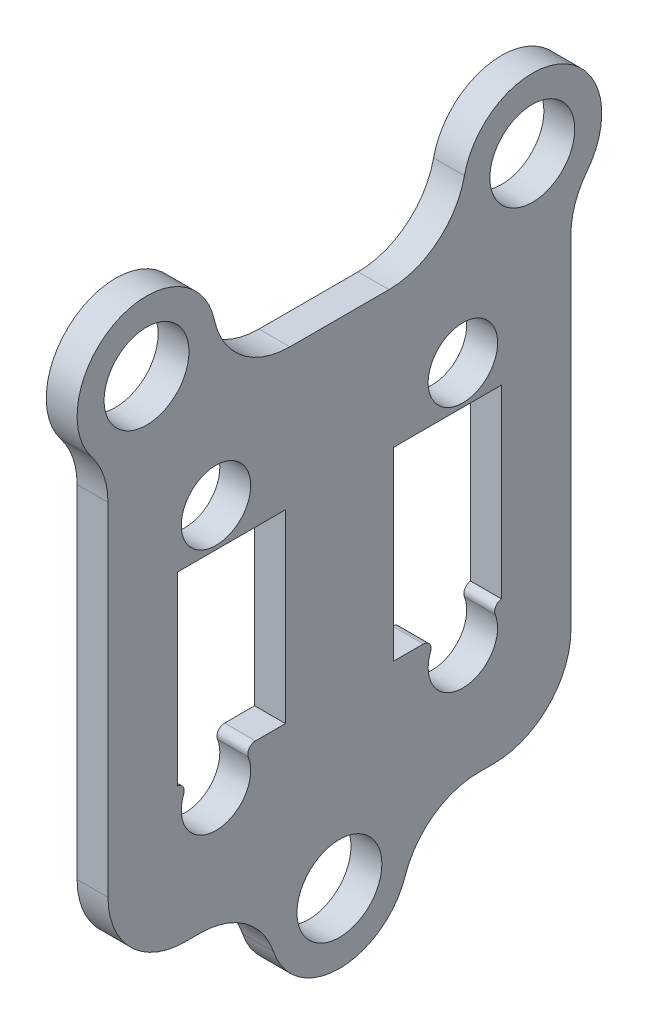
SolidWorks part; units mm, degrees
material "ABS"
ref_plane "Front Plane" through (0, 0, 0) normal (0, 0, 1) x (1, 0, 0)
ref_plane "Top Plane" through (0, 0, 0) normal (0, 1, 0) x (1, 0, 0)
ref_plane "Right Plane" through (0, 0, 0) normal (1, 0, 0) x (0, 0, -1)
sketch "Sketch1" plane through (0, 0, 0) normal (1, 0, 0) x (0, 0, -1)
  line L1 (-15, -15) -> (15, -15)
  line L2 (-15, -15) -> (-15, 15)
  line L3 (-15, 15) -> (15, 15)
  line L4 (15, -15) -> (15, 15)
  line L5 (-15, -15) -> (15, 15) construction
  line L6 (-15, 15) -> (15, -15) construction
  point P0 (0, 0)
  dimension "D1" = 30
extrude "Boss-Extrude1" add sketch "Sketch1" along normal blind 2
sketch "Sketch2" plane through (2, 0, 0) normal (1, 0, 0) x (0, 0, -1)
  line L0 (-3.5, 0) -> (0, 0) construction
  line L1 (-10.5, 6) -> (-3.5, 6)
  line L2 (-10.5, 6) -> (-10.5, -6)
  line L3 (-10.5, -6) -> (-3.5, -6)
  line L4 (-3.5, 6) -> (-3.5, -6)
  line L5 (3.5, 6) -> (10.5, 6)
  line L6 (3.5, 6) -> (3.5, -6)
  line L7 (3.5, -6) -> (10.5, -6)
  line L8 (10.5, 6) -> (10.5, -6)
  line L9 (0, 0) -> (3.5, 0) construction
  dimension "D1" = 12
  dimension "D2" = 7
  dimension "D3" = 10.5
extrude "Cut-Extrude1" cut sketch "Sketch2" against normal through all
hole_wizard "M4 Clearance Hole1" positions "Sketch3" profile "Sketch4" hole size "M4" standard "ANSI Metric" end condition through all
sketch "Sketch3" plane through (2, 0, 0) normal (1, 0, 0) x (0, 0, -1)
  line L0 (-8, 8.5) -> (8, 8.5) construction
  line L1 (8, 8.5) -> (8, -7.5) construction
  line L2 (8, -7.5) -> (-8, -7.5) construction
  line L3 (-8, -7.5) -> (-8, 8.5) construction
  line L5 (-10.5, 6) -> (-10.5, -6) construction
  line L8 (-3.5, 6) -> (-10.5, 6) construction
  point P0 (-8, 8.5)
  point P2 (-8, -7.5)
  point P4 (8, 8.5)
  point P6 (8, -7.5)
  point P18 (-10.5, 0)
  point P29 (-7, 6)
  point P30 (0, 8.5)
  dimension "D1" = 8.5
  dimension "D2" = 16
  dimension "D3" = 1
sketch "Sketch4" plane through (2, 8.5, 8) normal (0, 1, 0) x (0, 0, -1)
  line L0 (0, 0) -> (0, 2)
  line L1 (0, 2) -> (2.25, 2)
  line L2 (2.25, 2) -> (2.25, 0)
  line L5 (2.25, 0) -> (0, 0)
  line L11 (0, -6.35) -> (0, 107.95) construction
  dimension "Thru Hole Dia." = 4.5
  dimension "Thru Hole Depth" = 2
sketch "Sketch5" plane through (2, 0, 0) normal (1, 0, 0) x (0, 0, -1)
  line L0 (-8, 8.5) -> (8, -7.5) construction
  line L1 (-8, -7.5) -> (8, 8.5) construction
  line L3 (-11.5, -11) -> (11.5, -11)
  line L4 (-11.5, -11) -> (-11.5, 12)
  line L5 (-11.5, 12) -> (11.5, 12)
  line L6 (11.5, -11) -> (11.5, 12)
  line L7 (-11.5, -11) -> (11.5, 12) construction
  line L8 (-11.5, 12) -> (11.5, -11) construction
  point P8 (0, 0.5)
  dimension "D1" = 23
ref_point "Point1"
sketch "Sketch6" plane through (2, 0, 0) normal (1, 0, 0) x (0, 0, -1)
  line L9 (15, -15) -> (15, 15) construction
  line L11 (-15, 15) -> (-15, -15) construction
  line L12 (15, 15) -> (-15, 15) construction
  line L13 (-12.5, 18) -> (12.5, 18) construction
  line L14 (-15, 14.2583) -> (-15, 15)
  line L15 (-15, 15) -> (-9.1459, 15)
  line L16 (15, 14.2583) -> (15, 15)
  line L17 (9.1459, 15) -> (15, 15)
  line L18 (-15, -15) -> (15, -15) construction
  line L19 (-4.0311, -15) -> (4.0311, -15)
  arc A1 (-15, 14.2583) -> (-9.1459, 15) centre (-12.5, 18) cw
  arc A2 (9.1459, 15) -> (15, 14.2583) centre (12.5, 18) cw
  arc A3 (-4.0311, -15) -> (4.0311, -15) centre (0, -17) ccw
  point P13 (0, -17)
  point P28 (0, 18)
  dimension "D3" = 2
  dimension "D5" = 4.5
  dimension "D2" = 4.5
  dimension "D1" = 3
  dimension "D6" = 25
extrude "Boss-Extrude2" add sketch "Sketch6" against normal up to surface (2 mm away) up to face at (0, 8.5, 5.75)
hole_wizard "M5 Clearance Hole1" positions "Sketch9" profile "Sketch10" hole size "M5" standard "ANSI Metric" end condition through all
sketch "Sketch9" plane through (2, 0, 0) normal (1, 0, 0) x (0, 0, -1)
  point P0 (-12.5, 18)
  point P3 (12.5, 18)
  point P6 (0, -17)
sketch "Sketch10" plane through (2, 18, 12.5) normal (0, 1, 0) x (0, 0, -1)
  line L0 (0, 0) -> (0, 2)
  line L1 (0, 2) -> (2.75, 2)
  line L2 (2.75, 2) -> (2.75, 0)
  line L5 (2.75, 0) -> (0, 0)
  line L11 (0, -6.35) -> (0, 107.95) construction
  dimension "Thru Hole Dia." = 5.5
  dimension "Thru Hole Depth" = 2
fillet "Fillet1" radius 5 8 edges at (1, -15, 4.0311) (1, -15, -4.0311) (1, 14.2583, -15) (1, 15, -9.1459) (1, 15, 9.1459) (1, 14.2583, 15) (1, -15, -15) (1, -15, 15)
fillet "Fillet2" radius 0.5 4 edges at (1, -6, -9.6771) (1, -6, -6.3229) (1, -6, 6.3229) (1, -6, 9.6771)
